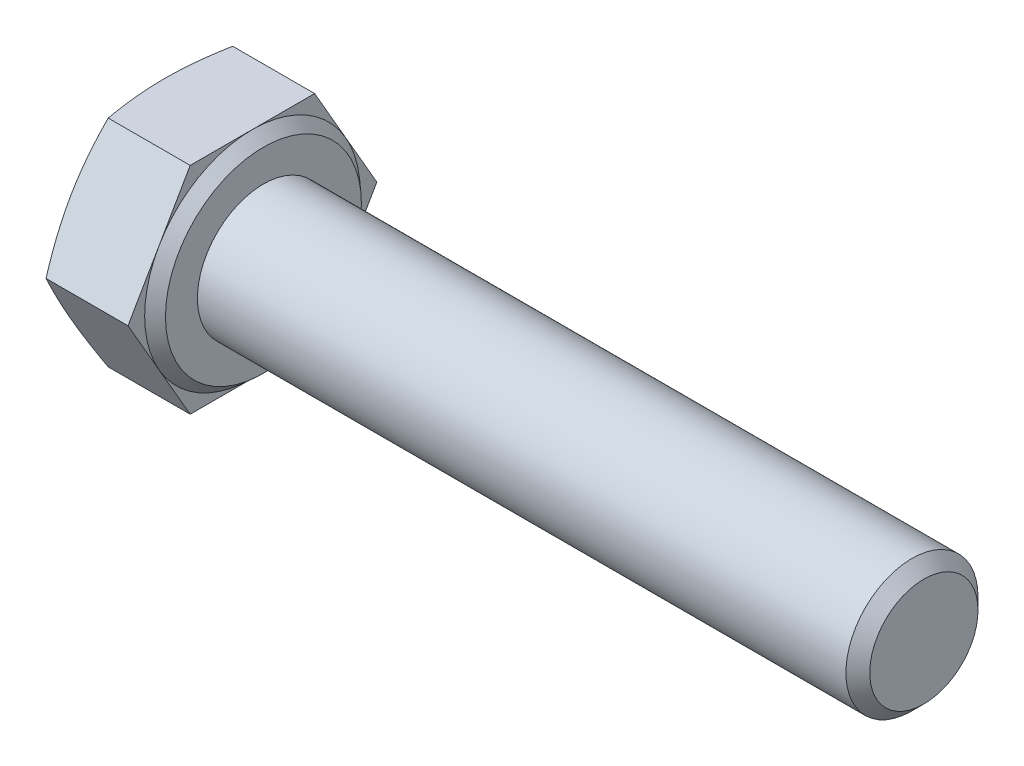
SolidWorks part; units mm, degrees
ref_plane "Front" through (0, 0, 0) normal (0, 0, 1) x (1, 0, 0)
ref_plane "Top" through (0, 0, 0) normal (0, 1, 0) x (1, 0, 0)
ref_plane "Right" through (0, 0, 0) normal (1, 0, 0) x (0, 0, -1)
sketch "Sketch-BaseHead" plane through (0, 0, 0) normal (1, 0, 0) x (0, 0, -1)
  line L1 (5.6523, 0) -> (2.8261, 4.895)
  line L2 (2.8261, 4.895) -> (-2.8261, 4.895)
  line L3 (-2.8261, 4.895) -> (-5.6523, 0)
  line L4 (-5.6523, 0) -> (-2.8261, -4.895)
  line L5 (-2.8261, -4.895) -> (2.8261, -4.895)
  line L6 (2.8261, -4.895) -> (5.6523, 0)
  circle A0 centre (0, 0) radius 4.895 construction
extrude "BaseHead" add sketch "Sketch-BaseHead" along normal blind 4
sketch "Sketch4" plane through (-0.2646, 0, 5.9169) normal (0, 1, 0) x (0, 0, -1)
  line L0 (5.9169, 3.7369) -> (5.9169, -10.4477) construction
  line L2 (11.5692, -0.2646) -> (10.8119, -0.2646)
  line L4 (10.8119, -0.2646) -> (11.5692, -0.5403)
  line L6 (11.5692, -0.5403) -> (11.5692, -0.2646)
  dimension "D1" = 20
  dimension "D2" = 9.79
revolve "HeadChamfer" cut sketch "Sketch4" angle 360 about L0
sketch "Sketch1" plane through (0, 0, 0) normal (0, 0, 1) x (1, 0, 0)
  line L0 (4, 0) -> (4.5, 0)
  line L1 (4.5, 0) -> (4.5, -4.45)
  line L2 (4.5, -4.45) -> (4, -4.895)
  line L3 (4, -4.895) -> (4, 0) construction
  line L4 (0, 0) -> (7.5821, 0) construction
  line L5 (-4.0016, 0) -> (10.1831, 0) construction
  line L6 (4, -4.895) -> (0.2756, -4.895) construction
  line L7 (4, 0) -> (4, -4.895)
  dimension "D1" = 4.895
  dimension "D2" = 4.45
revolve "Revolve1" add sketch "Sketch1" angle 360 about axis through (-4.0016, 0, 0) along (1, 0, 0)
ref_plane "Plane2" through (19.5, 0, 0) normal (1, 0, 0) x (0, 0, -1)
sketch "Sketch3" plane through (4.5, 0, 0) normal (1, 0, 0) x (0, 0, -1)
  circle A0 centre (0, 0) radius 3
extrude "BaseBody" add sketch "Sketch3" along normal blind 30
cosmetic thread "ThreadCosmetic1" [suppressed] parameters "b"=15, "D2"=4.917
fillet "HeadFillet" [suppressed] radius 0.25
chamfer "Chamfer1" distance 0.5415 angle 45 1 edges at (34.5, 0, -3)
sketch "Sketch5" plane through (0, 0, 0) normal (0, 0, 1) x (1, 0, 0)
  line L0 (33.417, 3.5415) -> (33.9585, 3.5415)
  line L1 (33.9585, 3.5415) -> (33.9585, 3)
  line L2 (33.9585, 3) -> (33.6877, 2.531)
  line L3 (33.6877, 2.531) -> (33.417, 3)
  line L4 (33.417, 3) -> (33.417, 3.5415)
  line L5 (33.9585, -3) -> (33.9585, 3) construction
  line L6 (33.9585, 3) -> (4.5, 3) construction
  dimension "D1" = 0.5415
revolve "Cut-Revolve10" [suppressed] cut sketch "Sketch5" angle 360
pattern_linear "LPattern10" [suppressed] count 23 of bodies 107
equation "\"D1@Sketch1\" = \"s@Sketch-BaseHead\"/ 2"
equation "\"D2@Sketch4\" = \"s@Sketch-BaseHead\""
equation "\"D1@Chamfer1\" =  ( \"d@Sketch3\" - \"D2@ThreadCosmetic1\" ) / 2 "
equation "\"b@ThreadCosmetic1\" = \"l@BaseBody\" - \"lg@Plane2\""
equation "\"D1@Sketch5\" =  (\"d@Sketch3\" - \"D2@ThreadCosmetic1\" )  / 2 "
equation "\"pitch@LPattern10\" = 1.2 * \"D1@Sketch5\""
equation "\"D1@LPattern10\" = \"b@ThreadCosmetic1\" / \"pitch@LPattern10\""
